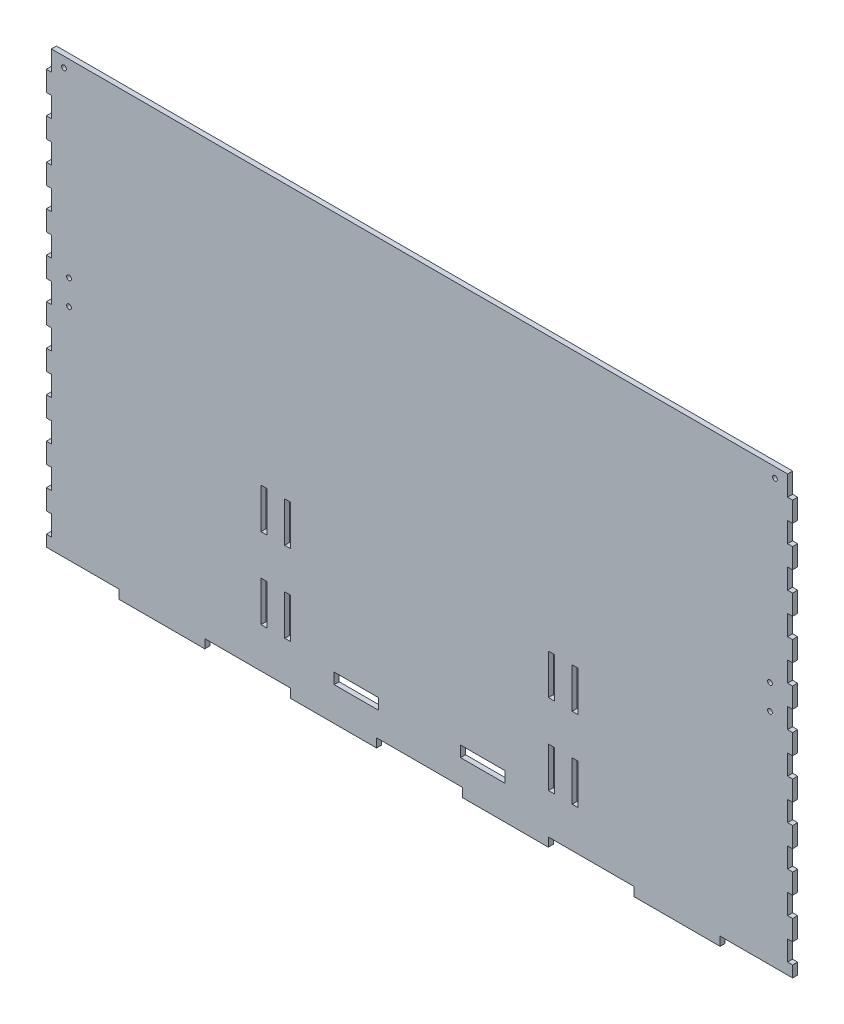
SolidWorks part; units mm, degrees
material "Acrylic (Medium-high impact)"
ref_plane "Front Plane" through (0, 0, 0) normal (0, 0, 1) x (1, 0, 0)
ref_plane "Top Plane" through (0, 0, 0) normal (0, 1, 0) x (1, 0, 0)
ref_plane "Right Plane" through (0, 0, 0) normal (1, 0, 0) x (0, 0, -1)
sketch "Sketch1" plane through (0, 0, 0) normal (0, 0, 1) x (1, 0, 0)
  line L0 (0, 139.7) -> (0, -139.7) construction
  line L1 (-406.4, 139.7) -> (406.4, 139.7)
  line L2 (-406.4, 139.7) -> (-406.4, -139.7)
  line L3 (-406.4, -139.7) -> (406.4, -139.7)
  line L4 (406.4, 139.7) -> (406.4, -139.7)
  line L49 (-381, 127) -> (-381, 114.3)
  line L54 (-381, 139.7) -> (-377.825, 139.7)
  line L55 (-381, 139.7) -> (-381, 127)
  line L56 (-381, 127) -> (-377.825, 127)
  line L57 (-377.825, 139.7) -> (-377.825, 127)
  line L58 (-381, 127) -> (-377.825, 127)
  line L59 (-377.825, 127) -> (-377.825, 114.3)
  line L60 (-381, 114.3) -> (-377.825, 114.3)
  line L61 (-381, 114.3) -> (-381, 101.6)
  line L62 (-381, 114.3) -> (-377.825, 114.3)
  line L63 (-377.825, 114.3) -> (-377.825, 101.6)
  line L64 (-381, 101.6) -> (-377.825, 101.6)
  line L65 (-381, 101.6) -> (-381, 88.9)
  line L66 (-381, 101.6) -> (-377.825, 101.6)
  line L67 (-377.825, 101.6) -> (-377.825, 88.9)
  line L68 (-381, 88.9) -> (-377.825, 88.9)
  line L69 (-381, 88.9) -> (-381, 76.2)
  line L70 (-381, 88.9) -> (-377.825, 88.9)
  line L71 (-377.825, 88.9) -> (-377.825, 76.2)
  line L72 (-381, 76.2) -> (-377.825, 76.2)
  line L73 (-381, 76.2) -> (-381, 63.5)
  line L74 (-381, 76.2) -> (-377.825, 76.2)
  line L75 (-377.825, 76.2) -> (-377.825, 63.5)
  line L76 (-381, 63.5) -> (-377.825, 63.5)
  line L77 (-381, 63.5) -> (-381, 50.8)
  line L78 (-381, 63.5) -> (-377.825, 63.5)
  line L79 (-377.825, 63.5) -> (-377.825, 50.8)
  line L80 (-381, 50.8) -> (-377.825, 50.8)
  line L81 (-381, 50.8) -> (-381, 38.1)
  line L82 (-381, 50.8) -> (-377.825, 50.8)
  line L83 (-377.825, 50.8) -> (-377.825, 38.1)
  line L84 (-381, 38.1) -> (-377.825, 38.1)
  line L85 (-381, 38.1) -> (-381, 25.4)
  line L86 (-381, 38.1) -> (-377.825, 38.1)
  line L87 (-377.825, 38.1) -> (-377.825, 25.4)
  line L88 (-381, 25.4) -> (-377.825, 25.4)
  line L89 (377.825, 127) -> (377.825, 114.3)
  line L90 (377.825, 139.7) -> (381, 139.7)
  line L91 (377.825, 139.7) -> (377.825, 127)
  line L92 (377.825, 127) -> (381, 127)
  line L93 (381, 139.7) -> (381, 127)
  line L94 (377.825, 127) -> (381, 127)
  line L95 (381, 127) -> (381, 114.3)
  line L96 (377.825, 114.3) -> (381, 114.3)
  line L97 (377.825, 114.3) -> (377.825, 101.6)
  line L98 (377.825, 114.3) -> (381, 114.3)
  line L99 (381, 114.3) -> (381, 101.6)
  line L100 (377.825, 101.6) -> (381, 101.6)
  line L101 (377.825, 101.6) -> (377.825, 88.9)
  line L102 (377.825, 101.6) -> (381, 101.6)
  line L103 (381, 101.6) -> (381, 88.9)
  line L104 (377.825, 88.9) -> (381, 88.9)
  line L105 (377.825, 88.9) -> (377.825, 76.2)
  line L106 (377.825, 88.9) -> (381, 88.9)
  line L107 (381, 88.9) -> (381, 76.2)
  line L108 (377.825, 76.2) -> (381, 76.2)
  line L109 (377.825, 76.2) -> (377.825, 63.5)
  line L110 (377.825, 76.2) -> (381, 76.2)
  line L111 (381, 76.2) -> (381, 63.5)
  line L112 (377.825, 63.5) -> (381, 63.5)
  line L113 (377.825, 63.5) -> (377.825, 50.8)
  line L114 (377.825, 63.5) -> (381, 63.5)
  line L115 (381, 63.5) -> (381, 50.8)
  line L116 (377.825, 50.8) -> (381, 50.8)
  line L117 (377.825, 50.8) -> (377.825, 38.1)
  line L118 (377.825, 50.8) -> (381, 50.8)
  line L119 (381, 50.8) -> (381, 38.1)
  line L120 (377.825, 38.1) -> (381, 38.1)
  line L121 (377.825, 38.1) -> (377.825, 25.4)
  line L122 (377.825, 38.1) -> (381, 38.1)
  line L123 (381, 38.1) -> (381, 25.4)
  line L124 (377.825, 25.4) -> (381, 25.4)
  line L125 (-352.2133, -134.112) -> (-352.2133, -139.7)
  line L126 (-406.4, -134.112) -> (-352.2133, -134.112)
  line L127 (-406.4, -134.112) -> (-406.4, -139.7)
  line L128 (-406.4, -139.7) -> (-352.2133, -139.7)
  line L129 (-352.2133, -134.112) -> (-352.2133, -139.7)
  line L130 (-352.2133, -134.112) -> (-298.0267, -134.112)
  line L131 (-298.0267, -134.112) -> (-298.0267, -139.7)
  line L132 (-352.2133, -139.7) -> (-298.0267, -139.7)
  line L133 (-298.0267, -134.112) -> (-298.0267, -139.7)
  line L134 (-298.0267, -134.112) -> (-243.84, -134.112)
  line L135 (-243.84, -134.112) -> (-243.84, -139.7)
  line L136 (-298.0267, -139.7) -> (-243.84, -139.7)
  line L137 (-243.84, -134.112) -> (-243.84, -139.7)
  line L138 (-243.84, -134.112) -> (-189.6533, -134.112)
  line L139 (-189.6533, -134.112) -> (-189.6533, -139.7)
  line L140 (-243.84, -139.7) -> (-189.6533, -139.7)
  line L141 (-189.6533, -134.112) -> (-189.6533, -139.7)
  line L142 (-189.6533, -134.112) -> (-135.4667, -134.112)
  line L143 (-135.4667, -134.112) -> (-135.4667, -139.7)
  line L144 (-189.6533, -139.7) -> (-135.4667, -139.7)
  line L145 (-135.4667, -134.112) -> (-135.4667, -139.7)
  line L146 (-135.4667, -134.112) -> (-81.28, -134.112)
  line L147 (-81.28, -134.112) -> (-81.28, -139.7)
  line L148 (-135.4667, -139.7) -> (-81.28, -139.7)
  line L149 (-81.28, -134.112) -> (-81.28, -139.7)
  line L150 (-81.28, -134.112) -> (-27.0933, -134.112)
  line L151 (-27.0933, -134.112) -> (-27.0933, -139.7)
  line L152 (-81.28, -139.7) -> (-27.0933, -139.7)
  line L153 (-27.0933, -134.112) -> (-27.0933, -139.7)
  line L154 (-27.0933, -134.112) -> (27.0933, -134.112)
  line L155 (27.0933, -134.112) -> (27.0933, -139.7)
  line L156 (-27.0933, -139.7) -> (27.0933, -139.7)
  line L157 (27.0933, -134.112) -> (27.0933, -139.7)
  line L158 (27.0933, -134.112) -> (81.28, -134.112)
  line L159 (81.28, -134.112) -> (81.28, -139.7)
  line L160 (27.0933, -139.7) -> (81.28, -139.7)
  line L161 (81.28, -134.112) -> (81.28, -139.7)
  line L162 (81.28, -134.112) -> (135.4667, -134.112)
  line L163 (135.4667, -134.112) -> (135.4667, -139.7)
  line L164 (81.28, -139.7) -> (135.4667, -139.7)
  line L165 (135.4667, -134.112) -> (135.4667, -139.7)
  line L166 (135.4667, -134.112) -> (189.6533, -134.112)
  line L167 (189.6533, -134.112) -> (189.6533, -139.7)
  line L168 (135.4667, -139.7) -> (189.6533, -139.7)
  line L169 (189.6533, -134.112) -> (189.6533, -139.7)
  line L170 (189.6533, -134.112) -> (243.84, -134.112)
  line L171 (243.84, -134.112) -> (243.84, -139.7)
  line L172 (189.6533, -139.7) -> (243.84, -139.7)
  line L173 (243.84, -134.112) -> (243.84, -139.7)
  line L174 (243.84, -134.112) -> (298.0267, -134.112)
  line L175 (298.0267, -134.112) -> (298.0267, -139.7)
  line L176 (243.84, -139.7) -> (298.0267, -139.7)
  line L177 (298.0267, -134.112) -> (298.0267, -139.7)
  line L178 (298.0267, -134.112) -> (352.2133, -134.112)
  line L179 (352.2133, -134.112) -> (352.2133, -139.7)
  line L180 (298.0267, -139.7) -> (352.2133, -139.7)
  line L181 (352.2133, -134.112) -> (352.2133, -139.7)
  line L182 (352.2133, -134.112) -> (406.4, -134.112)
  line L183 (406.4, -134.112) -> (406.4, -139.7)
  line L184 (352.2133, -139.7) -> (406.4, -139.7)
  line L205 (-90.678, 84.5227) -> (-90.678, -139.7) construction
  line L206 (90.678, 84.5227) -> (90.678, -139.7) construction
  line L207 (-90.678, -27.5886) -> (90.678, -27.5886) construction
  line L208 (-381, 25.4) -> (-381, 12.7)
  line L209 (-381, 25.4) -> (-377.825, 25.4)
  line L210 (-377.825, 25.4) -> (-377.825, 12.7)
  line L211 (-381, 12.7) -> (-377.825, 12.7)
  line L212 (-381, 12.7) -> (-381, 0)
  line L213 (-381, 12.7) -> (-377.825, 12.7)
  line L214 (-377.825, 12.7) -> (-377.825, 0)
  line L215 (-381, 0) -> (-377.825, 0)
  line L224 (-377.825, 0) -> (377.825, 0) construction
  line L229 (377.825, 25.4) -> (377.825, 12.7)
  line L230 (377.825, 25.4) -> (381, 25.4)
  line L231 (381, 25.4) -> (381, 12.7)
  line L232 (377.825, 12.7) -> (381, 12.7)
  line L233 (377.825, 12.7) -> (377.825, 0)
  line L234 (377.825, 12.7) -> (381, 12.7)
  line L235 (381, 12.7) -> (381, 0)
  line L236 (377.825, 0) -> (381, 0)
  line L237 (-381, 0) -> (-381, -12.7)
  line L238 (-381, 0) -> (-377.825, 0)
  line L239 (-377.825, 0) -> (-377.825, -12.7)
  line L240 (-381, -12.7) -> (-377.825, -12.7)
  line L241 (-381, -12.7) -> (-381, -25.4)
  line L242 (-381, -12.7) -> (-377.825, -12.7)
  line L243 (-377.825, -12.7) -> (-377.825, -25.4)
  line L244 (-381, -25.4) -> (-377.825, -25.4)
  line L245 (-381, -25.4) -> (-381, -38.1)
  line L246 (-381, -25.4) -> (-377.825, -25.4)
  line L247 (-377.825, -25.4) -> (-377.825, -38.1)
  line L248 (-381, -38.1) -> (-377.825, -38.1)
  line L249 (-381, -38.1) -> (-381, -50.8)
  line L250 (-381, -38.1) -> (-377.825, -38.1)
  line L251 (-377.825, -38.1) -> (-377.825, -50.8)
  line L252 (-381, -50.8) -> (-377.825, -50.8)
  line L253 (-381, -50.8) -> (-381, -63.5)
  line L254 (-381, -50.8) -> (-377.825, -50.8)
  line L255 (-377.825, -50.8) -> (-377.825, -63.5)
  line L256 (-381, -63.5) -> (-377.825, -63.5)
  line L257 (-381, -63.5) -> (-381, -76.2)
  line L258 (-381, -63.5) -> (-377.825, -63.5)
  line L259 (-377.825, -63.5) -> (-377.825, -76.2)
  line L260 (-381, -76.2) -> (-377.825, -76.2)
  line L261 (-381, -76.2) -> (-381, -88.9)
  line L262 (-381, -76.2) -> (-377.825, -76.2)
  line L263 (-377.825, -76.2) -> (-377.825, -88.9)
  line L264 (-381, -88.9) -> (-377.825, -88.9)
  line L265 (-381, -88.9) -> (-381, -101.6)
  line L266 (-381, -88.9) -> (-377.825, -88.9)
  line L267 (-377.825, -88.9) -> (-377.825, -101.6)
  line L268 (-381, -101.6) -> (-377.825, -101.6)
  line L269 (-381, -101.6) -> (-381, -114.3)
  line L270 (-381, -101.6) -> (-377.825, -101.6)
  line L271 (-377.825, -101.6) -> (-377.825, -114.3)
  line L272 (-381, -114.3) -> (-377.825, -114.3)
  line L273 (-381, -114.3) -> (-381, -127)
  line L274 (-381, -114.3) -> (-377.825, -114.3)
  line L275 (-377.825, -114.3) -> (-377.825, -127)
  line L276 (-381, -127) -> (-377.825, -127)
  line L277 (-381, -127) -> (-381, -139.7)
  line L278 (-381, -127) -> (-377.825, -127)
  line L279 (-377.825, -127) -> (-377.825, -139.7)
  line L280 (-381, -139.7) -> (-377.825, -139.7)
  line L281 (377.825, 0) -> (377.825, -12.7)
  line L282 (377.825, 0) -> (381, 0)
  line L283 (381, 0) -> (381, -12.7)
  line L284 (377.825, -12.7) -> (381, -12.7)
  line L285 (377.825, -12.7) -> (377.825, -25.4)
  line L286 (377.825, -12.7) -> (381, -12.7)
  line L287 (381, -12.7) -> (381, -25.4)
  line L288 (377.825, -25.4) -> (381, -25.4)
  line L289 (377.825, -25.4) -> (377.825, -38.1)
  line L290 (377.825, -25.4) -> (381, -25.4)
  line L291 (381, -25.4) -> (381, -38.1)
  line L292 (377.825, -38.1) -> (381, -38.1)
  line L293 (377.825, -38.1) -> (377.825, -50.8)
  line L294 (377.825, -38.1) -> (381, -38.1)
  line L295 (381, -38.1) -> (381, -50.8)
  line L296 (377.825, -50.8) -> (381, -50.8)
  line L297 (377.825, -50.8) -> (377.825, -63.5)
  line L298 (377.825, -50.8) -> (381, -50.8)
  line L299 (381, -50.8) -> (381, -63.5)
  line L300 (377.825, -63.5) -> (381, -63.5)
  line L301 (377.825, -63.5) -> (377.825, -76.2)
  line L302 (377.825, -63.5) -> (381, -63.5)
  line L303 (381, -63.5) -> (381, -76.2)
  line L304 (377.825, -76.2) -> (381, -76.2)
  line L305 (377.825, -76.2) -> (377.825, -88.9)
  line L306 (377.825, -76.2) -> (381, -76.2)
  line L307 (381, -76.2) -> (381, -88.9)
  line L308 (377.825, -88.9) -> (381, -88.9)
  line L309 (377.825, -88.9) -> (377.825, -101.6)
  line L310 (377.825, -88.9) -> (381, -88.9)
  line L311 (381, -88.9) -> (381, -101.6)
  line L312 (377.825, -101.6) -> (381, -101.6)
  line L313 (377.825, -101.6) -> (377.825, -114.3)
  line L314 (377.825, -101.6) -> (381, -101.6)
  line L315 (381, -101.6) -> (381, -114.3)
  line L316 (377.825, -114.3) -> (381, -114.3)
  line L317 (377.825, -114.3) -> (377.825, -127)
  line L318 (377.825, -114.3) -> (381, -114.3)
  line L319 (381, -114.3) -> (381, -127)
  line L320 (377.825, -127) -> (381, -127)
  line L321 (377.825, -127) -> (377.825, -139.7)
  line L322 (377.825, -127) -> (381, -127)
  line L323 (381, -127) -> (381, -139.7)
  line L324 (377.825, -139.7) -> (381, -139.7)
  point P6 (0, 0)
  point P128 (0, -27.5886)
  point P153 (0, 0)
  dimension "D4" = 12.7
  dimension "D5" = 3.175
  dimension "D10" = 181.356
  dimension "D12" = 755.65
  dimension "D8" = 812.8
  dimension "D11" = 54.1867
  dimension "D2" = 273.812
  dimension "D9" = 279.4
  dimension "D3" = 22
  dimension "D7" = 15
  dimension "D6" = 22
extrude "Main Extrude" add sketch "Sketch1" along normal blind 3.175 contours L321 L317 L313 L309 L305 L301 L297 L293 L289 L285 L281 L233 L229 L121 L117 L113 L109 L105 L101 L97 L89 L91 L1 L57 L59 L63 L67 L71 L75 L79 L83 L87 L210 L214 L239 L243 L247 L251 L255 L259 L263 L267 L271 L275 L279 L126 L130 L134 L138 L142 L146 | L277 L273 L269 L265 L261 L257 L253 L249 L245 L241 L237 L212 L208 L85 L81 L77 L73 L69 L65 L61 L49 L55 L1 L2 L126 | L319 L323 L182 L4 L1 L93 L95 L99 L103 L107 L111 L115 L119 L123 L231 L235 L283 L287 L291 L295 L299 L303 L307 L311 L315 | L126 L279 L3 L125 | L135 L134 L131 L3 | L143 L142 L139 L3 | L151 L150 L147 L3 | L159 L158 L155 L3 | L167 L166 L163 L3 | L175 L174 L171 L3 | L323 L182 L321 L184 | L89 L96 L95 L92 | L101 L104 L103 L100 | L109 L112 L111 L108 | L117 L120 L119 L116 | L229 L232 L231 L124 | L281 L284 L283 L236 | L289 L292 L291 L288 | L297 L300 L299 L296 | L305 L308 L307 L304 | L313 L316 L315 L312 | L323 L320 L321 L182 | L49 L60 L59 L56 | L65 L68 L67 L64 | L73 L76 L75 L72 | L81 L84 L83 L80 | L208 L211 L210 L88 | L237 L240 L239 L215 | L245 L248 L247 L244 | L253 L256 L255 L252 | L261 L264 L263 L260 | L269 L272 L271 L268 | L279 L276 L277 L126 | L277 L126 L2 L3 | L321 L182 L179 L3 | L182 L323 L3 L4 | L279 L126 L277 L128 region at (-393.7, 2.794, 0) region at (-393.7, -136.906, 0) region at (0, 2.794, 0) region at (-379.4125, 120.65, 0) region at (-379.4125, -130.556, 0) region at (-379.4125, -136.906, 0) region at (-365.0192, -136.906, 0) region at (393.7, 2.794, 0) region at (379.4125, 120.65, 0) region at (-379.4125, 95.25, 0) region at (-379.4125, -107.95, 0) region at (-270.9333, -136.906, 0) region at (393.7, -136.906, 0) region at (379.4125, 95.25, 0) region at (-379.4125, 69.85, 0) region at (-379.4125, -82.55, 0) region at (379.4125, -136.906, 0) region at (379.4125, -130.556, 0) region at (-162.56, -136.906, 0) region at (365.0192, -136.906, 0) region at (379.4125, 69.85, 0) region at (-379.4125, 44.45, 0) region at (-379.4125, -57.15, 0) region at (379.4125, -107.95, 0) region at (-54.1867, -136.906, 0) region at (270.9333, -136.906, 0) region at (379.4125, 44.45, 0) region at (-379.4125, 19.05, 0) region at (-379.4125, -31.75, 0) region at (379.4125, -82.55, 0) region at (54.1867, -136.906, 0) region at (162.56, -136.906, 0) region at (379.4125, 19.05, 0) region at (-379.4125, -6.35, 0) region at (379.4125, -57.15, 0) region at (379.4125, -6.35, 0) region at (379.4125, -31.75, 0)
sketch "Sketch8" plane through (0, 0, 3.175) normal (0, 0, 1) x (1, 0, 0)
  line L0 (-406.4, 139.7) -> (-406.4, -139.7) construction
  line L1 (-381, 28.2575) -> (-384.175, 28.2575)
  line L2 (-381, 28.2575) -> (-381, -3.6195)
  line L3 (-381, -3.6195) -> (-384.175, -3.6195)
  line L4 (-384.175, 28.2575) -> (-384.175, -3.6195)
  line L5 (-406.4, -139.7) -> (-352.2133, -139.7) construction
  line L6 (381, 28.2575) -> (384.175, 28.2575)
  line L7 (381, 28.2575) -> (381, -3.6195)
  line L8 (381, -3.6195) -> (384.175, -3.6195)
  line L9 (384.175, 28.2575) -> (384.175, -3.6195)
  line L11 (-381, 88.9) -> (-381, 76.2) construction
  line L12 (-352.2133, -134.112) -> (-298.0267, -134.112) construction
  line L13 (381, 88.9) -> (381, 76.2) construction
  line L14 (-393.7, -120.65) -> (393.7, -120.65) construction
  circle A0 centre (-393.7, -120.65) radius 1.5
  circle A1 centre (393.7, -120.65) radius 1.5
  point P6 (0, -120.65)
  point P16 (-384.175, 12.319)
  dimension "D5" = 3
  dimension "D1" = 31.877
  dimension "D2" = 3.175
  dimension "D3" = 146.431
  dimension "D4" = 19.05
  dimension "D6" = 12.7
extrude "Mount Holes" cut sketch "Sketch8" against normal through all
sketch "Sketch3" plane through (0, 0, 3.175) normal (0, 0, 1) x (1, 0, 0)
  line L0 (-135.4667, -134.112) -> (-81.28, -134.112) construction
  line L1 (-96.52, 126.492) -> (-84.836, 126.492)
  line L2 (-96.52, 126.492) -> (-96.52, -134.112)
  line L3 (-96.52, -134.112) -> (-84.836, -134.112)
  line L4 (-84.836, 126.492) -> (-84.836, -134.112)
  line L5 (81.28, -134.112) -> (135.4667, -134.112) construction
  line L6 (84.836, 126.492) -> (96.52, 126.492)
  line L7 (84.836, 126.492) -> (84.836, -134.112)
  line L8 (84.836, -134.112) -> (96.52, -134.112)
  line L9 (96.52, 126.492) -> (96.52, -134.112)
  line L10 (-84.836, -3.81) -> (84.836, -3.81) construction
  line L12 (-106.553, 10.3505) -> (-74.803, 10.3505)
  line L13 (-106.553, 10.3505) -> (-106.553, 0.8255)
  line L14 (-106.553, 0.8255) -> (-74.803, 0.8255)
  line L15 (-74.803, 10.3505) -> (-74.803, 0.8255)
  line L16 (74.803, 10.3505) -> (106.553, 10.3505)
  line L17 (74.803, 10.3505) -> (74.803, 0.8255)
  line L18 (74.803, 0.8255) -> (106.553, 0.8255)
  line L19 (106.553, 10.3505) -> (106.553, 0.8255)
  line L20 (-96.52, 126.492) -> (-92.6465, 126.492)
  line L21 (-96.52, 126.492) -> (-96.52, 82.042)
  line L22 (-96.52, 82.042) -> (-92.6465, 82.042)
  line L23 (-92.6465, 126.492) -> (-92.6465, 82.042)
  line L24 (-84.836, 126.492) -> (-88.7095, 126.492)
  line L25 (-84.836, 126.492) -> (-84.836, 82.042)
  line L26 (-84.836, 82.042) -> (-88.7095, 82.042)
  line L27 (-88.7095, 126.492) -> (-88.7095, 82.042)
  line L28 (84.836, 126.492) -> (88.7095, 126.492)
  line L29 (84.836, 126.492) -> (84.836, 82.042)
  line L30 (84.836, 82.042) -> (88.7095, 82.042)
  line L31 (88.7095, 126.492) -> (88.7095, 82.042)
  line L32 (96.52, 126.492) -> (92.6465, 126.492)
  line L33 (96.52, 126.492) -> (96.52, 82.042)
  line L34 (96.52, 82.042) -> (92.6465, 82.042)
  line L35 (92.6465, 126.492) -> (92.6465, 82.042)
  point P14 (-90.678, 126.492)
  point P15 (90.678, 126.492)
  point P16 (0, -3.81)
  point P27 (-90.678, 10.3505)
  point P28 (90.678, 10.3505)
  point P29 (-74.803, 5.588)
  dimension "D1" = 11.684
  dimension "D2" = 260.604
  dimension "D3" = 181.356
  dimension "D4" = 9.525
  dimension "D5" = 139.7
  dimension "D6" = 31.75
  dimension "D8" = 3.937
  dimension "D7" = 44.45
extrude "Door Slots" [suppressed] cut sketch "Sketch3" against normal through all contours L2 L12 L4 L1 | L2 L14 L4 L12 | L15 L12 L4 L14 | L13 L14 L2 L12 | L14 L2 L3 L4 | L7 L16 L9 L6 | L7 L18 L9 L16 | L19 L16 L9 L18 | L17 L18 L7 L16 | L18 L7 L8 L9
sketch "Sketch4" plane through (0, 0, 0) normal (0, 0, 1) x (1, 0, 0)
  line L1 (-81.28, -139.7) -> (-27.0933, -139.7) construction
  line L2 (-55.48, -112.41) -> (-52.178, -112.41)
  line L3 (-52.178, -112.41) -> (-52.178, -106.172)
  line L4 (-52.178, -106.172) -> (-2.178, -106.172)
  line L5 (-2.178, -106.172) -> (-2.178, -112.41)
  line L6 (-2.178, -112.41) -> (1.124, -112.41)
  line L9 (-55.48, -112.41) -> (-55.48, -134.112)
  line L10 (-55.48, -134.112) -> (-52.178, -134.112)
  line L11 (-52.178, -134.112) -> (-52.178, -139.7)
  line L12 (1.124, -112.41) -> (1.124, -134.112)
  line L13 (1.124, -134.112) -> (-2.178, -134.112)
  line L14 (-2.178, -134.112) -> (-2.178, -139.7)
  line L15 (-52.178, -139.7) -> (-2.178, -139.7)
  line L16 (-27.0933, -134.112) -> (27.0933, -134.112) construction
  line L17 (-27.0933, -134.112) -> (27.0933, -134.112) construction
  line L18 (12.128, -115.022) -> (42.228, -115.022)
  line L19 (12.128, -115.022) -> (12.128, -121.88)
  line L20 (12.128, -121.88) -> (42.228, -121.88)
  line L21 (42.228, -115.022) -> (42.228, -121.88)
  line L24 (-96.52, -134.112) -> (-84.836, -134.112) construction
  line L25 (84.836, -134.112) -> (96.52, -134.112) construction
  point P9 (-27.178, -106.172)
  point P10 (-27.178, -139.7)
  point P22 (27.178, -121.88)
  point P25 (90.678, -134.112)
  point P26 (12.128, -118.451)
  point P30 (-90.678, -134.112)
  dimension "D1" = 50
  dimension "D2" = 3.302
  dimension "D4" = 21.702
  dimension "D5" = 30.1
  dimension "D6" = 6.858
  dimension "D9" = 63.5
  dimension "D8" = 63.5
  dimension "D3" = 27.94
  dimension "D7" = 15.661
extrude "Trough and Lever Holes" [suppressed] cut sketch "Sketch4" along normal through all contours L11 L15 L14 L13 L12 L6 L5 L4 L3 L2 L9 L10 | L21 L18 L19 L20
sketch "Sketch5" plane through (0, 0, 3.175) normal (0, 0, 1) x (1, 0, 0)
  line L0 (-90.678, 126.492) -> (-90.678, -134.112) construction
  line L1 (-96.52, 126.492) -> (-84.836, 126.492) construction
  line L2 (-96.52, -134.112) -> (-84.836, -134.112) construction
  line L3 (90.678, 126.492) -> (90.678, -134.112) construction
  line L4 (84.836, 126.492) -> (96.52, 126.492) construction
  line L5 (84.836, -134.112) -> (96.52, -134.112) construction
  line L6 (-135.4667, -134.112) -> (-81.28, -134.112) construction
  line L19 (-99.998, -134.112) -> (-96.3199, -134.112)
  line L20 (-99.998, -134.112) -> (-99.998, -108.712)
  line L21 (-99.998, -108.712) -> (-96.3199, -108.712)
  line L22 (-96.3199, -134.112) -> (-96.3199, -108.712)
  line L24 (-99.998, -108.712) -> (-96.3199, -108.712)
  line L25 (-99.998, -108.712) -> (-99.998, -83.312)
  line L26 (-99.998, -83.312) -> (-96.3199, -83.312)
  line L27 (-96.3199, -108.712) -> (-96.3199, -83.312)
  line L28 (-96.3199, -83.312) -> (-99.998, -83.312)
  line L29 (-96.3199, -83.312) -> (-96.3199, -57.912)
  line L30 (-96.3199, -57.912) -> (-99.998, -57.912)
  line L31 (-99.998, -83.312) -> (-99.998, -57.912)
  line L32 (-99.998, -57.912) -> (-96.3199, -57.912)
  line L33 (-99.998, -57.912) -> (-99.998, -32.512)
  line L34 (-99.998, -32.512) -> (-96.3199, -32.512)
  line L35 (-96.3199, -57.912) -> (-96.3199, -32.512)
  line L36 (-96.3199, -32.512) -> (-99.998, -32.512)
  line L37 (-96.3199, -32.512) -> (-96.3199, -7.112)
  line L38 (-96.3199, -7.112) -> (-99.998, -7.112)
  line L39 (-99.998, -32.512) -> (-99.998, -7.112)
  line L40 (-81.358, -108.712) -> (-85.0361, -108.712)
  line L41 (-85.0361, -134.112) -> (-85.0361, -108.712)
  line L42 (-81.358, -134.112) -> (-85.0361, -134.112)
  line L43 (-81.358, -134.112) -> (-81.358, -108.712)
  line L44 (-81.358, -83.312) -> (-85.0361, -83.312)
  line L45 (-85.0361, -108.712) -> (-85.0361, -83.312)
  line L46 (-81.358, -108.712) -> (-85.0361, -108.712)
  line L47 (-81.358, -108.712) -> (-81.358, -83.312)
  line L48 (-85.0361, -57.912) -> (-81.358, -57.912)
  line L49 (-81.358, -83.312) -> (-81.358, -57.912)
  line L50 (-85.0361, -83.312) -> (-81.358, -83.312)
  line L51 (-85.0361, -83.312) -> (-85.0361, -57.912)
  line L52 (-81.358, -32.512) -> (-85.0361, -32.512)
  line L53 (-85.0361, -57.912) -> (-85.0361, -32.512)
  line L54 (-81.358, -57.912) -> (-85.0361, -57.912)
  line L55 (-81.358, -57.912) -> (-81.358, -32.512)
  line L56 (-85.0361, -7.112) -> (-81.358, -7.112)
  line L57 (-81.358, -32.512) -> (-81.358, -7.112)
  line L58 (-85.0361, -32.512) -> (-81.358, -32.512)
  line L59 (-85.0361, -32.512) -> (-85.0361, -7.112)
  line L60 (0, -1.7463) -> (0, 1.7463) construction
  line L61 (99.998, -108.712) -> (96.3199, -108.712)
  line L62 (96.3199, -134.112) -> (96.3199, -108.712)
  line L63 (99.998, -134.112) -> (96.3199, -134.112)
  line L64 (99.998, -134.112) -> (99.998, -108.712)
  line L65 (99.998, -83.312) -> (96.3199, -83.312)
  line L66 (96.3199, -108.712) -> (96.3199, -83.312)
  line L67 (99.998, -108.712) -> (96.3199, -108.712)
  line L68 (99.998, -108.712) -> (99.998, -83.312)
  line L69 (96.3199, -57.912) -> (99.998, -57.912)
  line L70 (99.998, -83.312) -> (99.998, -57.912)
  line L71 (96.3199, -83.312) -> (99.998, -83.312)
  line L72 (96.3199, -83.312) -> (96.3199, -57.912)
  line L73 (99.998, -32.512) -> (96.3199, -32.512)
  line L74 (96.3199, -57.912) -> (96.3199, -32.512)
  line L75 (99.998, -57.912) -> (96.3199, -57.912)
  line L76 (99.998, -57.912) -> (99.998, -32.512)
  line L77 (96.3199, -7.112) -> (99.998, -7.112)
  line L78 (99.998, -32.512) -> (99.998, -7.112)
  line L79 (96.3199, -32.512) -> (99.998, -32.512)
  line L80 (96.3199, -32.512) -> (96.3199, -7.112)
  line L81 (85.0361, -32.512) -> (85.0361, -7.112)
  line L82 (85.0361, -32.512) -> (81.358, -32.512)
  line L83 (81.358, -32.512) -> (81.358, -7.112)
  line L84 (85.0361, -7.112) -> (81.358, -7.112)
  line L85 (81.358, -57.912) -> (81.358, -32.512)
  line L86 (81.358, -57.912) -> (85.0361, -57.912)
  line L87 (85.0361, -57.912) -> (85.0361, -32.512)
  line L88 (81.358, -32.512) -> (85.0361, -32.512)
  line L89 (85.0361, -83.312) -> (85.0361, -57.912)
  line L90 (85.0361, -83.312) -> (81.358, -83.312)
  line L91 (81.358, -83.312) -> (81.358, -57.912)
  line L92 (85.0361, -57.912) -> (81.358, -57.912)
  line L93 (81.358, -108.712) -> (81.358, -83.312)
  line L94 (81.358, -108.712) -> (85.0361, -108.712)
  line L95 (85.0361, -108.712) -> (85.0361, -83.312)
  line L96 (81.358, -83.312) -> (85.0361, -83.312)
  line L97 (81.358, -134.112) -> (81.358, -108.712)
  line L98 (81.358, -134.112) -> (85.0361, -134.112)
  line L99 (85.0361, -134.112) -> (85.0361, -108.712)
  line L100 (81.358, -108.712) -> (85.0361, -108.712)
  dimension "D1" = 25.4
  dimension "D3" = 5.6419
  dimension "D2" = 9.32
extrude "Door Guide Slots" cut sketch "Sketch5" against normal through all contours L21 L27 L26 L25 | L30 L35 L34 L33 | L48 L55 L52 L53 | L40 L47 L44 L45 | L86 L87 L82 L85 | L94 L95 L90 L93 | L69 L76 L73 L74 | L61 L68 L65 L66 region at (-98.1589, -96.012, 3.175) region at (-98.1589, -45.212, 3.175) region at (-83.1971, -96.012, 3.175) region at (-83.1971, -45.212, 3.175) region at (98.1589, -96.012, 3.175) region at (98.1589, -45.212, 3.175) region at (83.1971, -45.212, 3.175) region at (83.1971, -96.012, 3.175)
sketch "Sketch7" plane through (0, 0, 3.175) normal (0, 0, 1) x (1, 0, 0)
  line L0 (-25.908, -115.0065) -> (25.908, -115.0065) construction
  line L1 (-53.848, -111.562) -> (-25.908, -111.562)
  line L2 (-53.848, -111.562) -> (-53.848, -118.451)
  line L3 (-53.848, -118.451) -> (-25.908, -118.451)
  line L4 (-25.908, -111.562) -> (-25.908, -118.451)
  line L5 (53.848, -111.562) -> (25.908, -111.562)
  line L6 (53.848, -111.562) -> (53.848, -118.451)
  line L7 (53.848, -118.451) -> (25.908, -118.451)
  line L8 (25.908, -111.562) -> (25.908, -118.451)
  line L9 (0, -115.0065) -> (0, 0) construction
  line L10 (-96.52, -134.112) -> (-84.836, -134.112) construction
  line L12 (-135.4667, -134.112) -> (-81.28, -134.112) construction
  point P12 (-53.848, -115.0065)
  point P15 (-39.878, -111.562)
  point P18 (-90.678, -134.112)
  dimension "D1" = 6.889
  dimension "D2" = 27.94
  dimension "D3" = 50.8
  dimension "D4" = 19.1055
extrude "Lever Holes" cut sketch "Sketch7" against normal through all
sketch "Sketch10" [suppressed] plane through (0, 0, 3.175) normal (0, 0, 1) x (1, 0, 0)
  line L0 (-101.678, 127.492) -> (-79.678, 127.492) construction
  line L2 (-92.6465, 126.492) -> (-88.7095, 126.492) construction
  line L3 (-90.678, 127.492) -> (-90.678, 126.492) construction
  line L4 (79.678, 127.492) -> (101.678, 127.492) construction
  line L5 (90.678, 127.492) -> (90.678, 126.492) construction
  line L6 (88.7095, 126.492) -> (92.6465, 126.492) construction
  circle A0 centre (-101.678, 127.492) radius 1.5
  circle A1 centre (-79.678, 127.492) radius 1.5
  circle A2 centre (79.678, 127.492) radius 1.5
  circle A3 centre (101.678, 127.492) radius 1.5
  dimension "D1" = 3
  dimension "D2" = 22
  dimension "D3" = 1
extrude "Door Guide Mount Holes" [suppressed] cut sketch "Sketch10" against normal through all
sketch "Sketch12" plane through (0, 0, 3.175) normal (0, 0, 1) x (1, 0, 0)
  line L0 (-246.507, 20.193) -> (-246.507, 4.445) construction
  line L1 (-221.107, 20.193) -> (-221.107, 4.445) construction
  line L2 (-246.507, 20.193) -> (-221.107, 20.193) construction
  line L3 (-246.507, 4.445) -> (-221.107, 4.445) construction
  line L4 (-243.332, 133.35) -> (-224.282, 133.35) construction
  line L5 (-406.4, 139.7) -> (406.4, 139.7) construction
  line L6 (-233.807, 20.193) -> (-233.807, 133.35) construction
  line L7 (-243.84, -134.112) -> (-189.6533, -134.112) construction
  line L8 (0, -1.7463) -> (0, 1.7463) construction
  line L9 (233.807, 20.193) -> (233.807, 133.35) construction
  line L10 (243.332, 133.35) -> (224.282, 133.35) construction
  line L11 (246.507, 4.445) -> (221.107, 4.445) construction
  line L12 (246.507, 20.193) -> (221.107, 20.193) construction
  line L13 (221.107, 20.193) -> (221.107, 4.445) construction
  line L14 (246.507, 20.193) -> (246.507, 4.445) construction
  circle A0 centre (-246.507, 20.193) radius 1.5
  circle A1 centre (-246.507, 4.445) radius 1.5
  circle A2 centre (-221.107, 4.445) radius 1.5
  circle A3 centre (-221.107, 20.193) radius 1.5
  circle A4 centre (-243.332, 133.35) radius 1.5
  circle A5 centre (-224.282, 133.35) radius 1.5
  circle A6 centre (224.282, 133.35) radius 1.5
  circle A7 centre (243.332, 133.35) radius 1.5
  circle A8 centre (221.107, 20.193) radius 1.5
  circle A9 centre (221.107, 4.445) radius 1.5
  circle A10 centre (246.507, 4.445) radius 1.5
  circle A11 centre (246.507, 20.193) radius 1.5
  point P12 (-233.807, 133.35)
  dimension "D1" = 3
  dimension "D2" = 233.807
  dimension "D3" = 19.05
  dimension "D4" = 6.35
  dimension "D5" = 25.4
  dimension "D6" = 15.748
  dimension "D7" = 138.557
extrude "Extension Clip Holes" cut sketch "Sketch12" against normal through all
sketch "Sketch11" plane through (0, 0, 3.175) normal (0, 0, 1) x (1, 0, 0)
  line L0 (-232.2195, 139.7) -> (-232.2195, 127)
  line L1 (-232.2195, 127) -> (-235.3945, 127)
  line L2 (-235.3945, 127) -> (-235.3945, 114.3)
  line L3 (-235.3945, 114.3) -> (-232.2195, 114.3)
  line L4 (232.2195, 139.7) -> (232.2195, 127)
  line L5 (232.2195, 127) -> (235.3945, 127)
  line L6 (235.3945, 127) -> (235.3945, 114.3)
  line L7 (235.3945, 114.3) -> (232.2195, 114.3)
  line L9 (-381, 127) -> (-377.825, 127) construction
  line L10 (-377.825, 139.7) -> (-377.825, 127) construction
  line L11 (235.3945, 120.65) -> (-235.3945, 120.65) construction
  line L12 (-232.2195, 114.3) -> (-232.2195, 101.6)
  line L13 (-232.2195, 101.6) -> (-235.3945, 101.6)
  line L14 (-235.3945, 101.6) -> (-235.3945, 88.9)
  line L15 (-235.3945, 88.9) -> (-232.2195, 88.9)
  line L16 (232.2195, 114.3) -> (232.2195, 101.6)
  line L17 (232.2195, 101.6) -> (235.3945, 101.6)
  line L18 (235.3945, 101.6) -> (235.3945, 88.9)
  line L19 (235.3945, 88.9) -> (232.2195, 88.9)
  line L20 (-232.2195, 88.9) -> (-232.2195, 76.2)
  line L21 (-232.2195, 76.2) -> (-235.3945, 76.2)
  line L22 (-235.3945, 76.2) -> (-235.3945, 63.5)
  line L23 (-235.3945, 63.5) -> (-232.2195, 63.5)
  line L24 (232.2195, 88.9) -> (232.2195, 76.2)
  line L25 (232.2195, 76.2) -> (235.3945, 76.2)
  line L26 (235.3945, 76.2) -> (235.3945, 63.5)
  line L27 (235.3945, 63.5) -> (232.2195, 63.5)
  line L28 (-232.2195, 63.5) -> (-232.2195, 50.8)
  line L29 (-232.2195, 50.8) -> (-235.3945, 50.8)
  line L30 (-235.3945, 50.8) -> (-235.3945, 38.1)
  line L31 (-235.3945, 38.1) -> (-232.2195, 38.1)
  line L32 (232.2195, 63.5) -> (232.2195, 50.8)
  line L33 (232.2195, 50.8) -> (235.3945, 50.8)
  line L34 (235.3945, 50.8) -> (235.3945, 38.1)
  line L35 (235.3945, 38.1) -> (232.2195, 38.1)
  line L36 (-232.2195, 38.1) -> (-232.2195, 25.4)
  line L37 (-232.2195, 25.4) -> (-235.3945, 25.4)
  line L38 (-235.3945, 25.4) -> (-235.3945, 12.7)
  line L39 (-235.3945, 12.7) -> (-232.2195, 12.7)
  line L40 (232.2195, 38.1) -> (232.2195, 25.4)
  line L41 (232.2195, 25.4) -> (235.3945, 25.4)
  line L42 (235.3945, 25.4) -> (235.3945, 12.7)
  line L43 (235.3945, 12.7) -> (232.2195, 12.7)
  line L44 (-232.2195, 12.7) -> (-232.2195, 0)
  line L45 (-232.2195, 0) -> (-235.3945, 0)
  line L46 (-235.3945, 0) -> (-235.3945, -12.7)
  line L47 (-235.3945, -12.7) -> (-232.2195, -12.7)
  line L48 (232.2195, 12.7) -> (232.2195, 0)
  line L50 (232.2195, 0) -> (235.3945, 0)
  line L52 (235.3945, 0) -> (235.3945, -12.7)
  line L53 (235.3945, -12.7) -> (232.2195, -12.7)
  line L54 (-232.2195, -12.7) -> (-232.2195, -25.4)
  line L55 (-232.2195, -25.4) -> (-235.3945, -25.4)
  line L56 (-235.3945, -25.4) -> (-235.3945, -38.1)
  line L57 (-235.3945, -38.1) -> (-232.2195, -38.1)
  line L58 (232.2195, -12.7) -> (232.2195, -25.4)
  line L59 (232.2195, -25.4) -> (235.3945, -25.4)
  line L60 (235.3945, -25.4) -> (235.3945, -38.1)
  line L61 (235.3945, -38.1) -> (232.2195, -38.1)
  line L62 (-232.2195, -38.1) -> (-232.2195, -50.8)
  line L63 (-232.2195, -50.8) -> (-235.3945, -50.8)
  line L64 (-235.3945, -50.8) -> (-235.3945, -63.5)
  line L65 (-235.3945, -63.5) -> (-232.2195, -63.5)
  line L66 (232.2195, -38.1) -> (232.2195, -50.8)
  line L67 (232.2195, -50.8) -> (235.3945, -50.8)
  line L68 (235.3945, -50.8) -> (235.3945, -63.5)
  line L69 (235.3945, -63.5) -> (232.2195, -63.5)
  line L70 (-232.2195, -63.5) -> (-232.2195, -76.2)
  line L71 (-232.2195, -76.2) -> (-235.3945, -76.2)
  line L72 (-235.3945, -76.2) -> (-235.3945, -88.9)
  line L73 (-235.3945, -88.9) -> (-232.2195, -88.9)
  line L74 (232.2195, -63.5) -> (232.2195, -76.2)
  line L75 (232.2195, -76.2) -> (235.3945, -76.2)
  line L76 (235.3945, -76.2) -> (235.3945, -88.9)
  line L77 (235.3945, -88.9) -> (232.2195, -88.9)
  line L78 (-232.2195, -88.9) -> (-232.2195, -101.6)
  line L79 (-232.2195, -101.6) -> (-235.3945, -101.6)
  line L80 (-235.3945, -101.6) -> (-235.3945, -114.3)
  line L81 (-235.3945, -114.3) -> (-232.2195, -114.3)
  line L82 (232.2195, -88.9) -> (232.2195, -101.6)
  line L83 (232.2195, -101.6) -> (235.3945, -101.6)
  line L84 (235.3945, -101.6) -> (235.3945, -114.3)
  line L85 (235.3945, -114.3) -> (232.2195, -114.3)
  line L86 (-232.2195, -114.3) -> (-232.2195, -127)
  line L87 (-232.2195, -127) -> (-235.3945, -127)
  line L88 (-235.3945, -127) -> (-235.3945, -139.7)
  line L90 (232.2195, -114.3) -> (232.2195, -127)
  line L91 (232.2195, -127) -> (235.3945, -127)
  line L92 (235.3945, -127) -> (235.3945, -139.7)
  line L98 (-406.4, 139.7) -> (406.4, 139.7)
  line L99 (-406.4, 139.7) -> (-406.4, -139.7)
  line L100 (-406.4, -139.7) -> (406.4, -139.7)
  line L101 (406.4, 139.7) -> (406.4, -139.7)
  line L102 (-235.3945, -139.7) -> (-232.2195, -139.7)
  line L103 (235.3945, -139.7) -> (232.2195, -139.7)
  point P14 (-233.807, 127)
  point P15 (233.807, 114.3)
  point P18 (0, 120.65)
  dimension "D2" = 11
  dimension "D1" = 467.614
extrude "Extended Side Cut" [suppressed] cut sketch "Sketch11" against normal through all
extrude "Extension Center Cut" cut sketch "Sketch11<3>" against normal through all contours L99 L100 L39 L31 L23 L15 L2 L1 L98 | L101 L98 L80 L77 L76 L75 L72 L69 L68 L67 L64 L61 L60 L59 L56 L53 L52 L50 L100 region at (-320.0962, 0.0584, 3.175) region at (320.0962, 0.0584, 3.175)
sketch "Sketch11<3>" plane through (0, 0, 3.175) normal (0, 0, 1) x (1, 0, 0) same geometry as "Sketch11"
sketch "Sketch14" [suppressed] plane through (0, 0, 3.175) normal (0, 0, 1) x (1, 0, 0)
  line L1 (-232.2195, 139.7) -> (232.2195, 139.7)
  line L2 (-232.2195, 139.7) -> (-232.2195, 165.1)
  line L3 (-232.2195, 165.1) -> (232.2195, 165.1)
  line L4 (232.2195, 139.7) -> (232.2195, 165.1)
  dimension "D1" = 25.4
extrude "Extra Inch" [suppressed] add sketch "Sketch14" against normal up to surface (3.175 mm away) up to face at (-83.1971, -96.012, 0)
sketch "Sketch15" plane through (0, 0, 3.175) normal (0, 0, 1) x (1, 0, 0)
  line L1 (-232.2195, 139.7) -> (232.2195, 139.7)
  line L2 (-232.2195, 139.7) -> (-232.2195, 165.1)
  line L3 (-232.2195, 165.1) -> (232.2195, 165.1)
  line L4 (232.2195, 139.7) -> (232.2195, 165.1)
  dimension "D1" = 25.4
extrude "Back Extra Inch" [suppressed] add sketch "Sketch15" against normal up to surface (3.175 mm away) up to face at (-83.1971, -96.012, 0)
sketch "Sketch16" [suppressed] plane through (0, 0, 3.175) normal (0, 0, 1) x (1, 0, 0)
  line L1 (-232.2195, 139.7) -> (-406.4, 139.7)
  line L2 (-232.2195, 139.7) -> (-232.2195, 165.1)
  line L3 (-232.2195, 165.1) -> (-406.4, 165.1)
  line L4 (-406.4, 139.7) -> (-406.4, 165.1)
  dimension "D1" = 25.4
extrude "Extended Extra Inch" [suppressed] add sketch "Sketch16" against normal up to surface (3.175 mm away) up to face at (-83.1971, -96.012, 0)
equation "\"bottomThickness\"= .220in"
equation "\"wallThickness\"= .125in"
equation "\"D4@Sketch1\"=\"D9@Sketch1\"/\"D3@Sketch1\""
equation "\"D5@Sketch1\"=\"wallThickness\""
equation "\"D1@Main Extrude\" = \"wallThickness\""
equation "\"D1@Sketch3\"=\"wallThickness\"*2+.19in+.02in"
equation "\"D2@Sketch4\"=\"wallThickness\"+.005in"
equation "\"D11@Sketch1\"=\"D8@Sketch1\"/\"D7@Sketch1\""
equation "\"D9@Sketch1\"=\"D2@Sketch1\"+\"bottomThickness\""
equation "\"D3@Sketch5\"=(\"wallThickness\"*2+.19in+.04)/2-(\"wallThickness\"-\"wallThickness\"/tan(80))*cos(80)"
equation "\"D8@Sketch3\"=\"wallThickness\"+.03in"
equation "\"D4@Sketch4\"=\"wallThickness\"+18.4mm+.005in"
equation "\"D2@Sketch5\"=(\"wallThickness\"*2+.19in+.04)/2+\"wallThickness\"/sin(80)"
